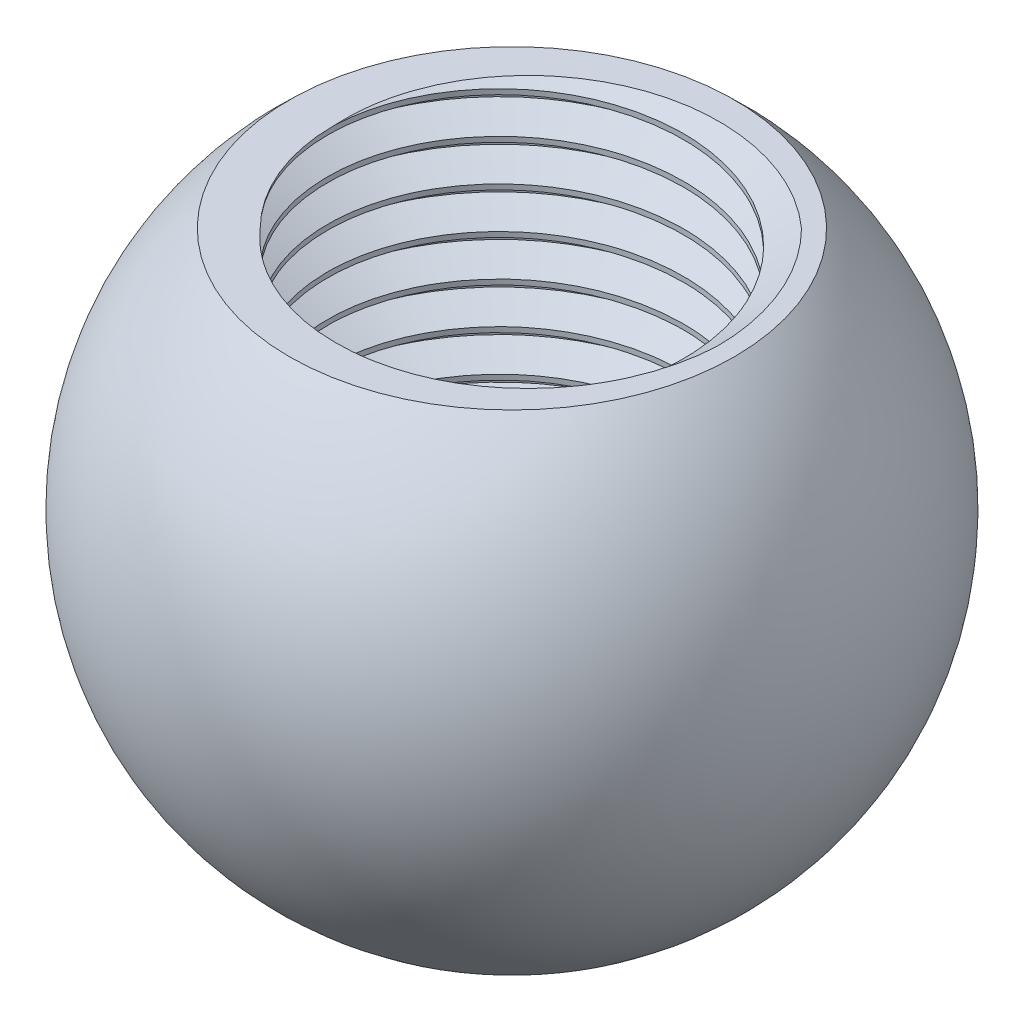
SolidWorks part; units mm, degrees
ref_plane "Alzado" through (0, 0, 0) normal (0, 0, 1) x (1, 0, 0)
ref_plane "Planta" through (0, 0, 0) normal (0, 1, 0) x (1, 0, 0)
ref_plane "Vista lateral" through (0, 0, 0) normal (1, 0, 0) x (0, 0, -1)
sketch "Croquis1" plane through (0, 0, 0) normal (0, 1, 0) x (1, 0, 0)
  circle A0 centre (0, 0) radius 6.75
  dimension "D1" = 13.5
extrude "Saliente-Extruir1" add sketch "Croquis1" along normal blind 14
hole_wizard "Perforador para roscar para macho de roscar para M12x1.251" positions "Croquis3D1" profile "Croquis2" hole size "M12x1.25" standard "Ansi Metric"
sketch3d "Croquis3D1"
  line L0 (0, 14, 0) -> (0, 0, 0) construction
  point P0 (0, 14, 0)
sketch "Croquis2" plane through (0, 14, 0) normal (1, 0, 0) x (0, 0, 1)
  line L0 (0, 0) -> (0, 12.2446)
  line L1 (0, 12.2446) -> (5.4, 9)
  line L2 (5.4, 9) -> (5.4, 0)
  line L5 (5.4, 0) -> (0, 0)
  line L10 (0, 12.2446) -> (-5.4, 9) construction
  line L11 (0, -6.35) -> (0, 107.95) construction
  dimension "Diámetro de taladro" = 10.8
  dimension "Profundidad de taladro" = 9
  dimension "Ángulo de perforador" = 118
sketch "Croquis3" plane through (0, 14, 0) normal (0, 1, 0) x (1, 0, 0)
  circle A0 centre (0, 0) radius 5.4 construction
  circle A1 centre (0, 0) radius 5.4
curve "Hélice/Espiral1" pitch 1.25 height 9 turns 7.2
ref_plane "Plano1" through (-5.4, 14, 0) normal (0, 0, 1) x (1, 0, 0)
sketch "Croquis4" plane through (-5.4, 14, 0) normal (0, 0, 1) x (1, 0, 0)
  line L0 (0, 0) -> (0, 1.0938) construction
  line L1 (0, 0.5469) -> (-0.9472, 0.5469) construction
  line L2 (-0.9472, 0.5469) -> (0, 1.0938) construction
  line L3 (-0.9472, 0.5469) -> (0, 0) construction
  line L4 (-0.9472, 0.5469) -> (-0.9472, 1.5203) construction
  line L5 (-0.8119, 0.5469) -> (-0.8119, 1.5203)
  line L6 (-0.8119, 0.625) -> (0, 1.0938)
  line L7 (0, 1.0938) -> (0, 0)
  line L8 (0, 0) -> (-0.8119, 0.4688)
  arc A0 (-0.8119, 0.625) -> (-0.8119, 0.4688) centre (-0.7668, 0.5469) ccw
  dimension "D1" = 1.0938
  dimension "D2" = 60
  dimension "D3" = 0.1353
sweep "Cortar-Barrer1" cut profiles "Croquis4" path "Hélice/Espiral1"
sketch "Croquis6" plane through (0, 0, 0) normal (0, 0, 1) x (1, 0, 0)
  line L0 (6.75, 14) -> (6.2119, 14)
  line L2 (6.75, 14) -> (-6.75, 14) construction
  line L3 (6.2119, 14) -> (6.2119, 1)
  line L4 (6.2119, 1) -> (0, 1)
  line L5 (0, 1) -> (0, -3.3782)
  arc A0 (0, -3.3782) -> (6.75, 14) centre (0, 6.6218) ccw
revolve "Revolución1" add sketch "Croquis6" angle 360 about L5
